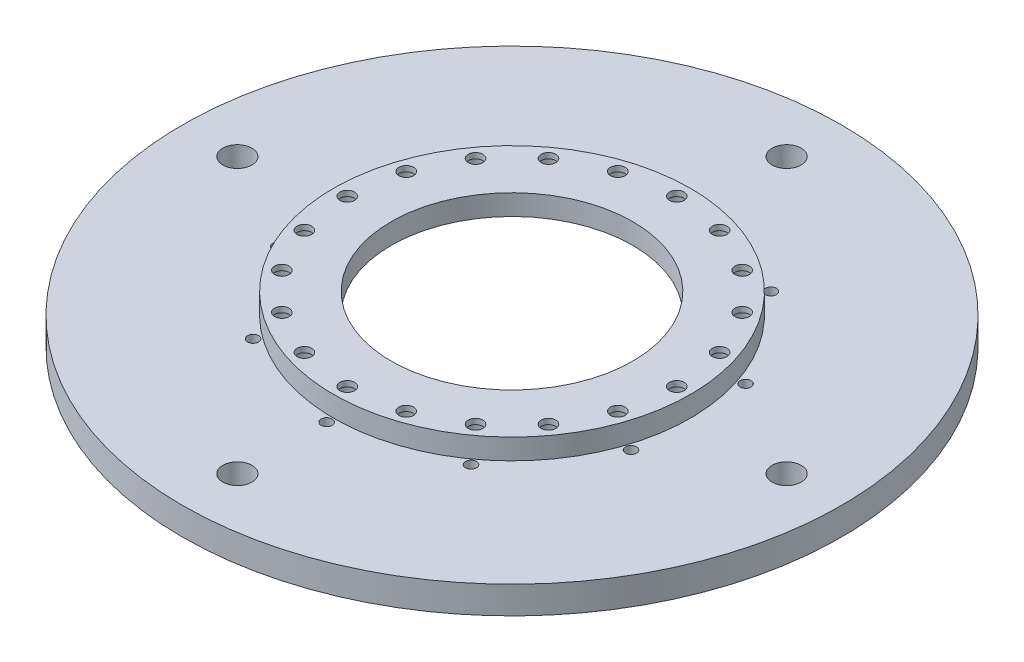
SolidWorks part; units mm, degrees
material "Plain Carbon Steel"
ref_plane "Front Plane" through (0, 0, 0) normal (0, 0, 1) x (1, 0, 0)
ref_plane "Top Plane" through (0, 0, 0) normal (0, 1, 0) x (1, 0, 0)
ref_plane "Right Plane" through (0, 0, 0) normal (1, 0, 0) x (0, 0, -1)
sketch "Sketch9" plane through (0, 0, 0) normal (0, 1, 0) x (1, 0, 0)
  circle A2 centre (0, 0) radius 82.55
  circle A4 centre (0, 0) radius 55.88
  circle A5 centre (0, 0) radius 76.2 construction
  point P6 (0, 76.2)
  point P34 (0, 0)
  dimension "Diameter_BackPlate" = 165.1
  dimension "Diameter_FuelOuterPlenum" = 111.76
  dimension "Diameter_BackPlate_BoltCircle" = 152.4
extrude "REF_BackPlate" add sketch "Sketch9" along normal blind 9.525 contours A2 A4 region at (-80.2151, 0, 0)
sketch "Sketch1" plane through (0, 0, 0) normal (0, 1, 0) x (1, 0, 0)
  line L1 (0, 82.55) -> (0, 81.788) construction
  line L2 (0, 81.788) -> (0, 76.2) construction
  line L6 (8.7416, 55.192) -> (13.4103, 84.6696) construction
  line L7 (0, 82.55) -> (0, 127) construction
  line L8 (39.2452, 120.7842) -> (25.5094, 78.5097) construction
  line L9 (8.7416, 55.192) -> (0, 0) construction
  circle A3 centre (0, 0) radius 152.4
  circle A8 centre (0, 0) radius 127 construction
  circle A14 centre (0, 76.2) radius 5.588 construction
  circle A15 centre (0, 0) radius 55.88 construction
  circle A17 centre (0, 0) radius 82.55 construction
  circle A18 centre (23.5471, 72.4705) radius 5.588 construction
  circle A19 centre (0, 0) radius 76.2 construction
  circle A20 centre (0, 0) radius 79.375
  circle A23 centre (0, 0) radius 85.725 construction
  arc A24 (0, 76.2) -> (23.5471, 72.4705) centre (0, 0) cw construction
  point P0 (8.7416, 55.192)
  point P2 (0, 127)
  point P5 (0, 85.725)
  point P12 (11.9203, 75.2619)
  dimension "Diameter_Takeout_BoltCircle" = 254
  dimension "Diameter_ThrustPlate" = 304.8
  dimension "D1" = 11.176
  dimension "D2" = 171.45
  dimension "D4" = 158.75
  dimension "D3" = 18
sketch "Sketch20" plane through (0, 0, 0) normal (0, -1, 0) x (-1, 0, 0)
  point P0 (0, 76.2)
hole_wizard "REF_CBORE_BackPlate" positions "Sketch20" profile "Sketch21" counterbore size "1/4" standard "ANSI Inch" end condition through all
sketch "Sketch21" plane through (0, 0, -76.2) normal (1, 0, 0) x (0, 0, -1)
  line L0 (0, 0) -> (0, 9.525)
  line L1 (0, 9.525) -> (3.3782, 9.525)
  line L3 (3.3782, 9.525) -> (3.3782, 6.985)
  line L4 (3.3782, 6.985) -> (5.588, 6.985)
  line L5 (5.588, 6.985) -> (5.588, 0)
  line L7 (5.588, 0) -> (0, 0)
  line L11 (0, -6.35) -> (0, 107.95) construction
  dimension "Thru Hole Dia." = 6.7564
  dimension "Thru Hole Depth" = 9.525
  dimension "C'Bore Dia." = 11.176
  dimension "C'Bore Depth" = 6.985
pattern_circular "REF_CBORE_BackPlate_Pattern" count 20 over 360 about axis through (0, 9.525, 0) along (0, -1, 0) of "REF_CBORE_BackPlate"
extrude "ThrustPlate_TC3" add sketch "Sketch1" against normal blind 12.7 separate body contours A3 region at (-148.0895, 0, 0)
sketch "Sketch11" plane through (0, 0, 0) normal (0, 1, 0) x (1, 0, 0)
  point P0 (0, 127)
hole_wizard "UNDEF_Clearance_ThrustPlate" positions "Sketch11" profile "Sketch12" hole size "1/2" standard "ANSI Inch" end condition through all
sketch "Sketch12" plane through (0, 0, -127) normal (1, 0, 0) x (0, 0, 1)
  line L0 (0, 0) -> (0, 12.7)
  line L1 (0, 12.7) -> (6.7462, 12.7)
  line L2 (6.7462, 12.7) -> (6.7462, 0)
  line L5 (6.7462, 0) -> (0, 0)
  line L11 (0, -6.35) -> (0, 107.95) construction
  dimension "Thru Hole Dia." = 13.4925
  dimension "Thru Hole Depth" = 12.7
pattern_circular "Clearance_ThrustPlate_Pattern" count 4 over 360 about axis through (0, -12.7, 0) along (0, 1, 0) of "UNDEF_Clearance_ThrustPlate" reverse direction yes
sketch "Sketch22" plane through (0, 0, 0) normal (0, 1, 0) x (1, 0, 0)
  point P0 (0, 85.725)
hole_wizard "#10 Clearance Hole1" positions "Sketch22" profile "Sketch23" hole size "#10" standard "ANSI Inch" end condition through all
sketch "Sketch23" plane through (0, 0, -85.725) normal (1, 0, 0) x (0, 0, 1)
  line L0 (0, 0) -> (0, 12.7)
  line L1 (0, 12.7) -> (2.5527, 12.7)
  line L2 (2.5527, 12.7) -> (2.5527, 0)
  line L5 (2.5527, 0) -> (0, 0)
  line L11 (0, -6.35) -> (0, 107.95) construction
  dimension "Thru Hole Dia." = 5.1054
  dimension "Thru Hole Depth" = 12.7
pattern_circular "CirPattern1" count 10 over 360 about axis through (0, -12.7, 0) along (0, 1, 0) of "#10 Clearance Hole1" reverse direction yes
equation "\"Diameter_BackPlate\"= 6.5"
equation "\"VAR_Diameter_BackPlate_BoltCircle\"= 6"
equation "\"VAR_Diameter_FuelOuterPlenum\"= 4.4"
equation "\"Diameter_BackPlate@Sketch9\"=\"Diameter_BackPlate\""
equation "\"Diameter_BackPlate_BoltCircle@Sketch9\"=\"VAR_Diameter_BackPlate_BoltCircle\""
equation "\"Diameter_FuelOuterPlenum@Sketch9\"=\"VAR_Diameter_FuelOuterPlenum\""
equation "\"Thickness_ThrustPlate\"= 0.5'undetermined"
equation "\"Diameter_ThrustPlate\"= 12'defined"
equation "\"Diameter_Takeout_BoltCicle\"= 10'defined"
equation "\"Diameter_Takeout_BoltCircle@Sketch1\"=\"Diameter_Takeout_BoltCicle\""
equation "\"Diameter_ThrustPlate@Sketch1\"=\"Diameter_ThrustPlate\""
equation "\"D1@ThrustPlate_TC3\"=\"Thickness_ThrustPlate\""
equation "\"VAR_Diameter_CBORE\"= 0.44'undetermined"
equation "\"VAR_Diameter_Clearance_ThrustPlate\"= 0.25'undetermined"
equation "\"D3@Sketch1\"=360/\"D1@REF_CBORE_BackPlate_Pattern\""
equation "\"D1@Sketch1\"=\"C'Bore Dia.@Sketch21\"''''''''''''''''''''''''''''''''''''''''''''''''''''''''''"
equation "\"C'Bore Dia.@Sketch21\"=\"VAR_Diameter_CBORE\""
equation "\"NumberBolts_BackPlate\"= 20"
equation "\"NumberBolts_Takeout\"= 4'defined"
equation "\"D1@Clearance_ThrustPlate_Pattern\"=\"NumberBolts_Takeout\""
equation "\"D1@REF_CBORE_BackPlate_Pattern\"=\"NumberBolts_BackPlate\""
